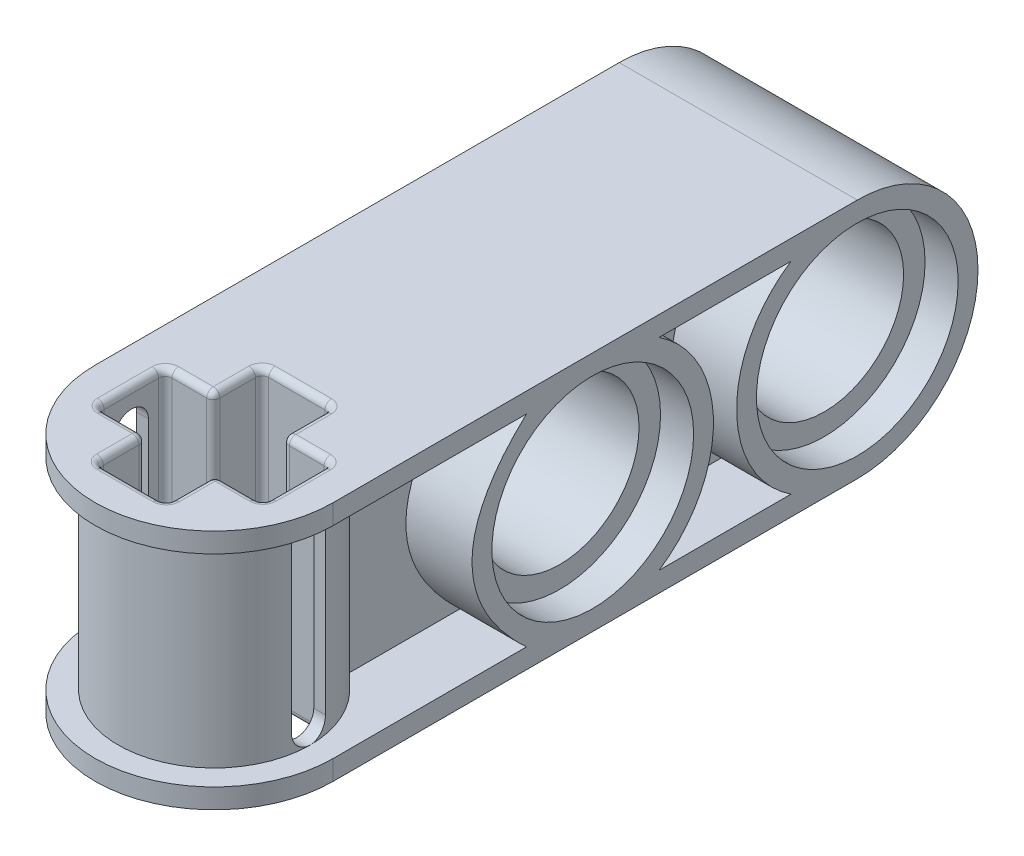
SolidWorks part; units mm, degrees
ref_plane "Front Plane" through (0, 0, 0) normal (0, 0, 1) x (1, 0, 0)
ref_plane "Top Plane" through (0, 0, 0) normal (0, 1, 0) x (1, 0, 0)
ref_plane "Right Plane" through (0, 0, 0) normal (1, 0, 0) x (0, 0, -1)
sketch "Sketch2" plane through (0, 0, 0) normal (1, 0, 0) x (0, 0, -1)
  line L0 (0, 0) -> (-20.6, 0) construction
  line L1 (0, -3.65) -> (-19.85, -3.65)
  line L2 (0, 3.65) -> (-19.85, 3.65)
  line L3 (2.4, -1000) -> (2.4, 49000) construction
  line L4 (-10.4, -1000) -> (-10.4, 49000) construction
  line L5 (3.65, -1000) -> (3.65, 49000) construction
  line L9 (-19.85, 3.65) -> (-19.85, -3.65)
  arc A0 (0, -3.65) -> (0, 3.65) centre (0, 0) ccw
  circle A2 centre (0, 0) radius 2.4
  circle A3 centre (0, 0) radius 3.05 construction
  circle A4 centre (-8, 0) radius 2.4
  circle A5 centre (-8, 0) radius 3.05 construction
  point P3 (-9.55, 0)
  point P8 (3.65, 0)
  dimension "D2" = 4.8
  dimension "D4" = 6.1
  dimension "D7" = 4.8
  dimension "D8" = 23.5
  dimension "D5" = 6.1
  dimension "D1" = 12.8
  dimension "D3" = 8
  dimension "D6" = 7.3
extrude "Boss-Extrude1" add sketch "Sketch2" along normal blind 7.2
sketch "Sketch3" plane through (0, 3.65, 0) normal (0, 1, 0) x (1, 0, 0)
  line L0 (3.6, -1000) -> (3.6, 49000) construction
  line L1 (7.2, 0) -> (0, 0) construction
  line L2 (-994.6662, 3.65) -> (49005.3338, 3.65) construction
  line L3 (2.55, -14.825) -> (1.1, -14.825)
  line L4 (-996.2, -19.85) -> (49003.8, -19.85) construction
  line L5 (4.65, -18.35) -> (2.55, -18.35)
  line L6 (4.65, -18.35) -> (4.65, -16.875)
  line L7 (4.65, -13.35) -> (2.55, -13.35)
  line L8 (2.55, -18.35) -> (2.55, -16.875)
  line L9 (4.65, -18.35) -> (2.55, -13.35) construction
  line L10 (4.65, -13.35) -> (2.55, -18.35) construction
  line L11 (6.1, -16.875) -> (4.65, -16.875)
  line L12 (6.1, -16.875) -> (6.1, -14.825)
  line L13 (6.1, -14.825) -> (4.65, -14.825)
  line L14 (1.1, -16.875) -> (1.1, -14.825)
  line L15 (6.1, -16.875) -> (1.1, -14.825) construction
  line L16 (6.1, -14.825) -> (1.1, -16.875) construction
  line L17 (2.55, -16.875) -> (1.1, -16.875)
  line L18 (2.55, -14.825) -> (2.55, -13.35)
  line L19 (4.65, -14.825) -> (4.65, -13.35)
  line L20 (7.2, -19.85) -> (0, -19.85) construction
  line L21 (-3.96, 0) -> (3.96, 0) construction
  line L22 (-996.3, -19.9) -> (49003.7, -19.9) construction
  line L23 (-996.3, -15.85) -> (49003.7, -15.85) construction
  line L24 (7.2, 3.65) -> (0, 3.65) construction
  circle A2 centre (3.6, -15.85) radius 2.702 construction
  arc A3 (-0.1, -15.85) -> (7.3, -15.85) centre (3.6, -15.85) ccw construction
  point P5 (3.6, 0)
  dimension "D1" = 17
  dimension "D2" = 3.7
  dimension "D3" = 2.05
  dimension "D4" = 1.475
  dimension "D5" = 19.5
  dimension "D6" = 3.65
extrude "Cut-Extrude1" cut sketch "Sketch3" along direction (0, -1, 0) on the side against the normal through all
sketch "Sketch4" plane through (0, 3.65, 0) normal (0, 1, 0) x (1, 0, 0)
  line L0 (-998.8, -15.85) -> (49001.2, -15.85) construction
  line L1 (1.1, -14.825) -> (1.1, -16.875) construction
  line L2 (3.6, -1013.7) -> (3.6, 48986.3) construction
  line L3 (4.65, -13.35) -> (2.55, -13.35) construction
  line L4 (7.2, 0) -> (7.2, -19.85) construction
  line L5 (-996, -19.45) -> (49004, -19.45) construction
  line L6 (-996, 3.65) -> (49004, 3.65) construction
  line L7 (7.2, 3.65) -> (0, 3.65) construction
  arc A0 (7.2, -15.85) -> (0, -15.85) centre (3.6, -15.85) cw
  point P5 (1.1, -15.85)
  point P10 (3.6, -13.35)
  point P18 (3.6, -19.45)
  point P23 (3.6, 3.65)
extrude "Cut-Extrude2" cut sketch "Sketch4" against normal blind 7.3 and the other way through all contours A0
sketch "Sketch5" plane through (7.2, 0, 0) normal (1, 0, 0) x (0, 0, -1)
  circle A0 centre (-8, 0) radius 3.05
  circle A1 centre (0, 0) radius 3.05
  dimension "D1" = 6.1
  dimension "D2" = 6.1
extrude "Cut-Extrude3" cut sketch "Sketch5" against normal blind 1
sketch "Sketch6" plane through (0, 0, 0) normal (-1, 0, 0) x (0, 0, 1)
  circle A0 centre (0, 0) radius 3.05
  circle A1 centre (8, 0) radius 3.05
extrude "Cut-Extrude4" cut sketch "Sketch6" against normal blind 1
sketch "Sketch8" plane through (7.2, 0, 0) normal (1, 0, 0) x (0, 0, -1)
  line L2 (-5.995, 3.05) -> (-2.005, 3.05)
  line L3 (-5.995, -3.05) -> (-2.005, -3.05)
  arc A0 (0, -3.65) -> (0, 3.65) centre (0, 0) ccw construction
  arc A7 (-2.005, 3.05) -> (-2.005, -3.05) centre (0, 0) ccw
  arc A8 (-5.995, -3.05) -> (-5.995, 3.05) centre (-8, 0) ccw
  point P9 (3.65, 0)
  point P10 (-3.65, 0)
  dimension "D1" = 7.3
extrude "Cut-Extrude5" cut sketch "Sketch8" against normal blind 2
ref_plane "Plane1" through (3.6, 0, 0) normal (1, 0, 0) x (0, 0, -1)
sketch "Sketch9" plane through (0, 0, 0) normal (-1, 0, 0) x (0, 0, 1)
  line L0 (2.005, 3.05) -> (5.995, 3.05)
  line L1 (2.005, -3.05) -> (5.995, -3.05)
  arc A0 (5.995, 3.05) -> (5.995, -3.05) centre (8, 0) ccw
  arc A1 (2.005, -3.05) -> (2.005, 3.05) centre (0, 0) ccw
  arc A2 (0, 3.65) -> (0, -3.65) centre (0, 0) ccw construction
  point P6 (3.65, 0)
  point P12 (-3.65, 0)
  dimension "D2" = 7.3
extrude "Cut-Extrude6" cut sketch "Sketch9" against normal blind 2
ref_plane "Plane3" through (0, 0, 15.85) normal (0, 0, 1) x (1, 0, 0)
ref_axis "Axis1" through (3.6, 3.65, 15.85) along (0, -1, 0)
sketch "Sketch15" plane through (7.2, 0, 0) normal (1, 0, 0) x (0, 0, -1)
  line L0 (-8, 3.65) -> (-15.85, 3.65)
  line L1 (-10.005, 3.05) -> (-13.4776, 3.05)
  line L4 (-13.4776, 3.05) -> (-13.4776, -3.05)
  line L5 (-13.4776, -3.05) -> (-10.005, -3.05)
  circle A0 centre (-8, 0) radius 3.65 construction
  spline S0 degree 2 poles (-10.005, 3.05) (-13.295, 0) (-10.005, -3.05) knots 0 0 0 1 1 1
extrude "Cut-Extrude10" cut sketch "Sketch15" against normal blind 2 contours S0 L1 L4 L5 region at (7.2, 0, 12.239)
sketch "Sketch13" plane through (0, 0, 15.85) normal (0, 0, 1) x (1, 0, 0)
  line L0 (-1000, 0) -> (49000, 0) construction
  line L1 (6.5, 3.05) -> (8.4505, 3.05)
  line L2 (6.5, 3.05) -> (6.5, -3.05)
  line L3 (6.5, -3.05) -> (8.4505, -3.05)
  line L4 (8.4505, 3.05) -> (8.4505, -3.05)
  line L5 (6.1, -3.65) -> (6.1, 3.65) construction
  line L6 (-993.0472, 3.65) -> (49006.9528, 3.65) construction
  line L8 (-996.4, -3.65) -> (49003.6, -3.65) construction
  line L9 (4.65, -3.65) -> (2.55, -3.65) construction
  point P14 (3.6, -3.65)
  dimension "D1" = 0.4
  dimension "D2" = 1.9505
  dimension "D3" = 6.1
  dimension "D4" = 3.05
  dimension "D5" = 7.3
revolve "Cut-Revolve2" cut sketch "Sketch13" angle 180 about axis through (3.6, 3.65, 15.85) along (0, -1, 0)
revolve "Cut-Revolve3" cut sketch "Sketch13<3>" angle 55 about axis through (3.6, 3.65, 15.85) along (0, -1, 0) reverse direction yes
sketch "Sketch13<3>" plane through (0, 0, 15.85) normal (0, 0, 1) x (1, 0, 0) same geometry as "Sketch13"
ref_plane "Plane4" through (3.6, 0, 0) normal (-1, 0, 0) x (0, 0, 1)
mirror "Mirror2" about plane through (3.6, 0, 0) normal (-1, 0, 0) of "Cut-Revolve3"
mirror "Mirror3" about plane through (3.6, 0, 0) normal (-1, 0, 0) of "Cut-Extrude10"
sketch "Sketch16" plane through (6.1, 0, 0) normal (-1, 0, 0) x (0, 0, 1)
  line L0 (15.85, 2.5369) -> (15.85, -2.5369) construction
  line L1 (15.85, -4.015) -> (15.85, 4.015) construction
  line L2 (15.85, 3.65) -> (15.85, -3.1942) construction
  line L3 (16.3631, 2.5369) -> (16.3631, -2.5369)
  line L4 (15.3369, 2.5369) -> (15.3369, -2.5369)
  line L5 (13.4776, 3.05) -> (18.75, 3.05) construction
  line L6 (15.85, -3.05) -> (10.005, -3.05) construction
  arc A0 (16.3631, 2.5369) -> (15.3369, 2.5369) centre (15.85, 2.5369) ccw
  arc A1 (15.3369, -2.5369) -> (16.3631, -2.5369) centre (15.85, -2.5369) ccw
  point P6 (15.85, 0)
  point P11 (15.85, 3.05)
  point P14 (15.85, -3.05)
extrude "Cut-Extrude11" cut sketch "Sketch16" along normal mid plane 200
fillet "Fillet1" radius 0.2 36 edges at (3.6, -3.65, 13.35) (3.6, 3.65, 13.35) (1.1, -3.65, 15.85) (1.1, 3.65, 15.85) (6.1, -3.65, 15.85) (6.1, 3.65, 15.85) (3.6, -3.65, 18.35) (3.6, 3.65, 18.35) (4.65, -3.65, 14.0875) (4.65, 0, 13.35) (4.65, 3.65, 14.0875) (2.55, 0, 13.35) (2.55, -3.65, 14.0875) (2.55, 3.65, 14.0875) (2.55, 0, 14.825) (1.825, -3.65, 14.825) (1.1, 0, 14.825) (1.825, 3.65, 14.825) (1.1, 0, 16.875) (1.825, -3.65, 16.875) (1.825, 3.65, 16.875) (6.1, 0, 14.825) (5.375, -3.65, 14.825) (4.65, 0, 14.825) (5.375, 3.65, 14.825) (5.375, -3.65, 16.875) (6.1, 0, 16.875) (5.375, 3.65, 16.875) (4.65, 0, 18.35) (4.65, -3.65, 17.6125) (4.65, 0, 16.875) (4.65, 3.65, 17.6125) (2.55, 0, 16.875) (2.55, -3.65, 17.6125) (2.55, 0, 18.35) (2.55, 3.65, 17.6125)
